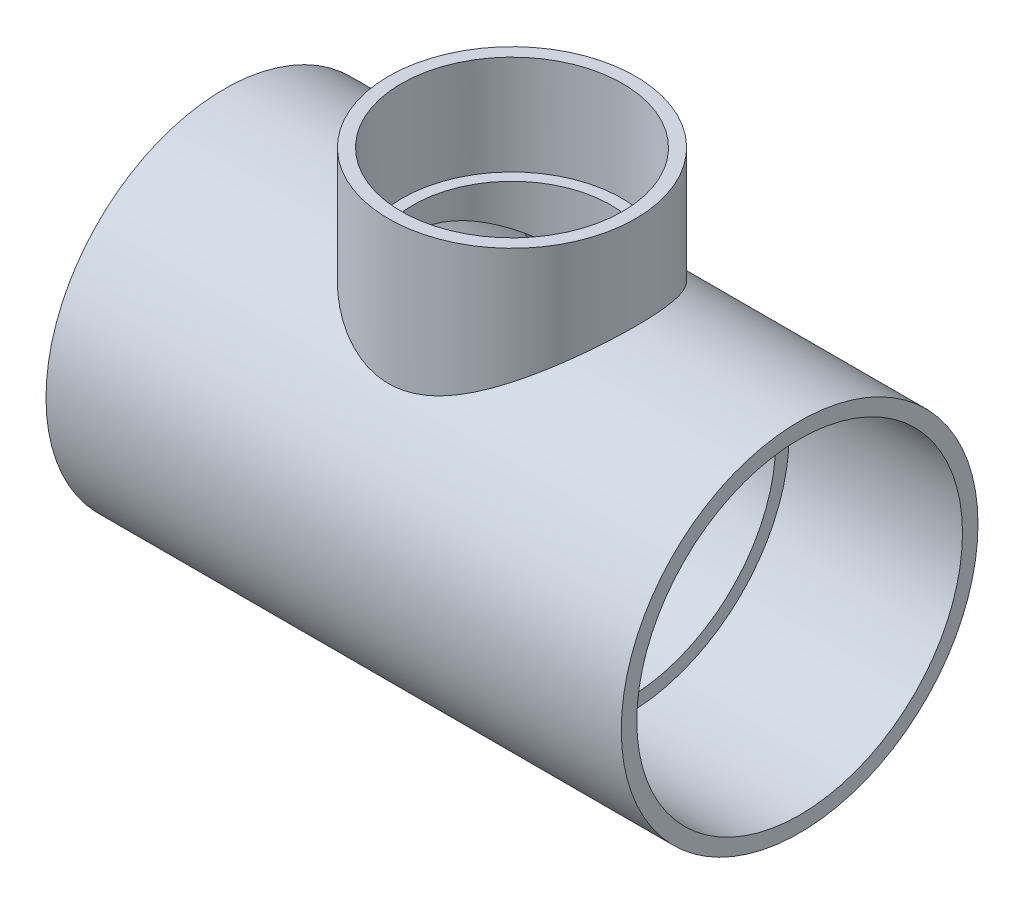
SolidWorks part; units mm, degrees
ref_plane "Front Plane" through (0, 0, 0) normal (0, 0, 1) x (1, 0, 0)
ref_plane "Top Plane" through (0, 0, 0) normal (0, 1, 0) x (1, 0, 0)
ref_plane "Right Plane" through (0, 0, 0) normal (1, 0, 0) x (0, 0, -1)
sketch "Sketch0" plane through (0, 0, 0) normal (0, 0, 1) x (1, 0, 0)
  line L0 (-149.098, 0) -> (0, 0) construction
  line L1 (0, 0) -> (0, 140.716) construction
  line L2 (-59.69, 0) -> (0, 0) construction
  line L3 (0, 0) -> (0, 89.408) construction
  line L4 (-149.098, 92.456) -> (-149.098, -92.456) construction
  line L5 (-59.69, 83.9978) -> (-149.098, 84.4169) construction
  line L6 (-59.69, 83.9978) -> (-59.69, -83.9978) construction
  line L7 (-59.69, -83.9978) -> (-149.098, -84.4169) construction
  line L8 (-149.098, 84.4169) -> (-149.098, -84.4169) construction
  line L9 (-64.008, 140.716) -> (64.008, 140.716) construction
  line L10 (-57.3786, 140.716) -> (57.3786, 140.716) construction
  line L11 (57.3786, 140.716) -> (57.0357, 89.408) construction
  line L12 (57.0357, 89.408) -> (-57.0357, 89.408) construction
  line L13 (-57.0357, 89.408) -> (-57.3786, 140.716) construction
  line L14 (-59.69, 77.0255) -> (-59.69, -77.0255) construction
  line L15 (-149.098, 0) -> (-59.69, 0) construction
  line L16 (0, 140.716) -> (0, 89.408) construction
  line L17 (0, 0) -> (59.69, 0) construction
  line L18 (-51.1302, 89.408) -> (51.1302, 89.408) construction
  line L19 (59.69, 0) -> (149.098, 0) construction
  dimension "H" = 149.098
  dimension "G" = 59.69
  dimension "M" = 184.912
  dimension "OD A" = 168.8338
  dimension "OD B" = 167.9956
  dimension "ID" = 154.051
  dimension "H3" = 140.716
  dimension "G3" = 89.408
  dimension "M3" = 128.016
  dimension "OD A3" = 114.7572
  dimension "OD B3" = 114.0714
  dimension "ID3" = 102.2604
sketch "Sketch1" plane through (0, 0, 0) normal (0, 0, 1) x (1, 0, 0)
  line L0 (-149.098, 0) -> (0, 0) construction
  line L1 (-149.098, 0) -> (0, 0) construction
  line L2 (0, 0) -> (0, -92.456) construction
  line L3 (-149.098, -92.456) -> (-59.69, -92.456)
  line L4 (-149.098, -92.456) -> (-149.098, -84.4169)
  line L5 (-149.098, -84.4169) -> (-59.69, -83.9978)
  line L6 (-59.69, -92.456) -> (-59.69, -83.9978)
  line L7 (-59.69, -92.456) -> (0, -92.456) construction
  line L8 (149.098, -84.4169) -> (59.69, -83.9978)
  line L9 (149.098, -92.456) -> (149.098, -84.4169)
  line L10 (59.69, -92.456) -> (59.69, -83.9978)
  line L11 (149.098, -92.456) -> (59.69, -92.456)
revolve "Revolve1" add sketch "Sketch1" angle 360 about L1
sketch "Sketch2" plane through (0, 0, 0) normal (0, 0, 1) x (1, 0, 0)
  line L0 (57.3786, 140.716) -> (57.0357, 89.408)
  line L1 (57.0357, 89.408) -> (64.008, 89.408)
  line L2 (64.008, 89.408) -> (64.008, 140.716)
  line L3 (64.008, 140.716) -> (57.3786, 140.716)
  line L4 (0, 0) -> (0, 140.716) construction
  line L5 (0, 0) -> (0, 140.716) construction
revolve "Revolve2" add sketch "Sketch2" angle 360 about L5
sketch "Sketch3" plane through (-59.69, 0, 0) normal (1, 0, 0) x (0, 0, -1)
  circle A0 centre (0, 0) radius 77.0255
  circle A1 centre (0, 0) radius 92.456
sketch "Sketch4" plane through (-59.69, 0, 0) normal (1, 0, 0) x (0, 0, -1)
  circle A0 centre (0, 0) radius 92.456 construction
  circle A1 centre (0, 0) radius 92.456
extrude "Boss-Extrude1" add sketch "Sketch4" along normal up to vertex (119.38 mm away) up to point (59.69, 0, 0)
sketch "Sketch5" plane through (0, 89.408, 0) normal (0, -1, 0) x (1, 0, 0)
  circle A0 centre (0, 0) radius 64.008 construction
  circle A1 centre (0, 0) radius 64.008
extrude "Boss-Extrude2" add sketch "Sketch5" along normal up to vertex (89.408 mm away) up to point (0, 0, 0)
sketch "Sketch6" plane through (0, 0, 0) normal (0, 0, 1) x (1, 0, 0)
  line L0 (-149.098, -84.4169) -> (-59.69, -83.9978)
  line L1 (-59.69, -83.9978) -> (-59.69, -77.0255)
  line L2 (-59.69, -77.0255) -> (59.69, -77.0255)
  line L3 (59.69, -83.9978) -> (59.69, 80.7558) construction
  line L4 (0, -77.0255) -> (0, 0) construction
  line L5 (59.69, -83.9978) -> (59.69, -77.0255)
  line L6 (149.098, -84.4169) -> (149.098, 84.4169) construction
  line L7 (149.098, -92.456) -> (149.098, 92.456) construction
  line L8 (149.098, -84.4169) -> (149.098, 0)
  line L9 (149.098, 0) -> (-149.098, 0)
  line L10 (-149.098, 0) -> (-149.098, -84.4169)
  line L11 (149.098, -84.4169) -> (59.69, -83.9978)
revolve "Cut-Revolve1" cut sketch "Sketch6" angle 360 about L9
sketch "Sketch7" plane through (0, 0, 0) normal (0, 0, 1) x (1, 0, 0)
  line L0 (57.3786, 140.716) -> (57.0357, 89.408)
  line L1 (57.0357, 89.408) -> (51.1302, 89.408)
  line L2 (51.1302, 89.408) -> (51.1302, 0)
  line L3 (0, 0) -> (59.69, 0) construction
  line L4 (51.1302, 0) -> (0, 0)
  line L5 (0, 0) -> (0, 140.716)
  line L6 (-64.008, 140.716) -> (64.008, 140.716) construction
  line L7 (0, 140.716) -> (57.3786, 140.716)
revolve "Cut-Revolve2" cut sketch "Sketch7" angle 360 about L5
other "CPoint1" parameters "Diameter"=101.6, "StubLength"=76.2
ref_axis "Axis1" through (0, 99.408, 0) along (0, -1, 0)
other "CPoint2" parameters "Diameter"=152.4, "StubLength"=76.2
ref_axis "Axis2" through (-69.69, 0, 0) along (1, 0, 0)
other "CPoint3" parameters "Diameter"=152.4, "StubLength"=76.2
ref_axis "Axis3" through (69.69, 0, 0) along (-1, 0, 0)
other "RPoint1"
